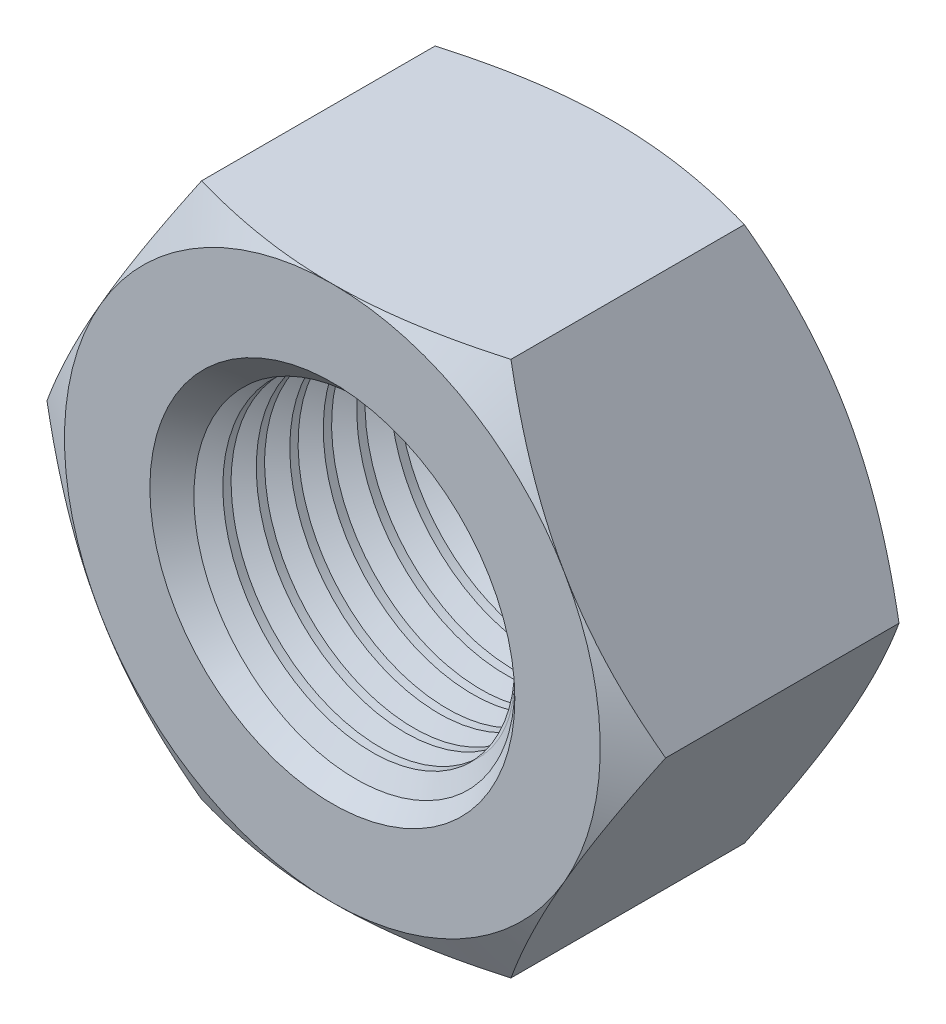
SolidWorks part; units mm, degrees
ref_plane "Front" through (0, 0, 0) normal (0, 0, 1) x (1, 0, 0)
ref_plane "Top" through (0, 0, 0) normal (0, 1, 0) x (1, 0, 0)
ref_plane "Right" through (0, 0, 0) normal (1, 0, 0) x (0, 0, -1)
sketch "Çizim1" plane through (0, 0, 0) normal (0, 0, 1) x (1, 0, 0)
  line L1 (46.188, 0) -> (23.094, 40)
  line L2 (23.094, 40) -> (-23.094, 40)
  line L3 (-23.094, 40) -> (-46.188, 0)
  line L4 (-46.188, 0) -> (-23.094, -40)
  line L5 (-23.094, -40) -> (23.094, -40)
  line L6 (23.094, -40) -> (46.188, 0)
  circle A0 centre (0, 0) radius 40 construction
  point P1 (0, 0)
  point P10 (0, 0)
  dimension "D1" = 80
extrude "Yükseklik-Ekstrüzyon1" add sketch "Çizim1" along normal blind 42
sketch "Çizim2" plane through (0, 0, 42) normal (0, 0, 1) x (1, 0, 0)
  circle A2 centre (0, 0) radius 40
extrude "Kes-Ekstrüzyon1" cut sketch "Çizim2" against normal blind 42 draft 60 flip side to cut
sketch "Çizim3" plane through (0, 0, 0) normal (0, 0, -1) x (-1, 0, 0)
  circle A0 centre (0, 0) radius 40
extrude "Kes-Ekstrüzyon2" cut sketch "Çizim3" against normal blind 42 draft 60 flip side to cut
sketch "Çizim4" plane through (0, 0, 42) normal (0, 0, 1) x (1, 0, 0)
  circle A0 centre (0, 0) radius 22.75
  dimension "D1" = 45.5
extrude "Kes-Ekstrüzyon3" cut sketch "Çizim4" against normal blind 42
chamfer "Pah1" distance 4.5 angle 45 2 edges at (22.75, 0, 0) (22.75, 0, 42)
sketch "Çizim5" plane through (0, 0, 0) normal (0, 0, -1) x (-1, 0, 0)
  circle A0 centre (0, 0) radius 22.75
curve "Helis/Spiral1" pitch 5 height 48 radius 22.75 centre (0, 0, 0) axis (0, 0, 1) start towards (1, 0, 0)
ref_plane "Düzlem1" through (-18.4051, -13.3721, 48) normal (0.5874, -0.8085, 0.035) x (-0.8093, -0.5869, 0.0254)
sketch "Çizim6" plane through (-18.4051, -13.3721, 48) normal (0.5874, -0.8085, 0.035) x (-0.8093, -0.5869, 0.0254)
  line L0 (-1.1032, 2.5133) -> (-1.1032, -2.5133)
  line L1 (3.25, 0) -> (-1.1032, 2.5133)
  line L3 (-1.1032, -2.5133) -> (3.25, 0)
  line L5 (-1.625, 2.8146) -> (-1.625, 0) [skipped]
  circle A0 centre (0, 0) radius 1.625 construction
  dimension "D1" = 3.25
sweep "Kes-Süpür1" cut profiles "Çizim6" path "Helis/Spiral1" align with end faces yes
